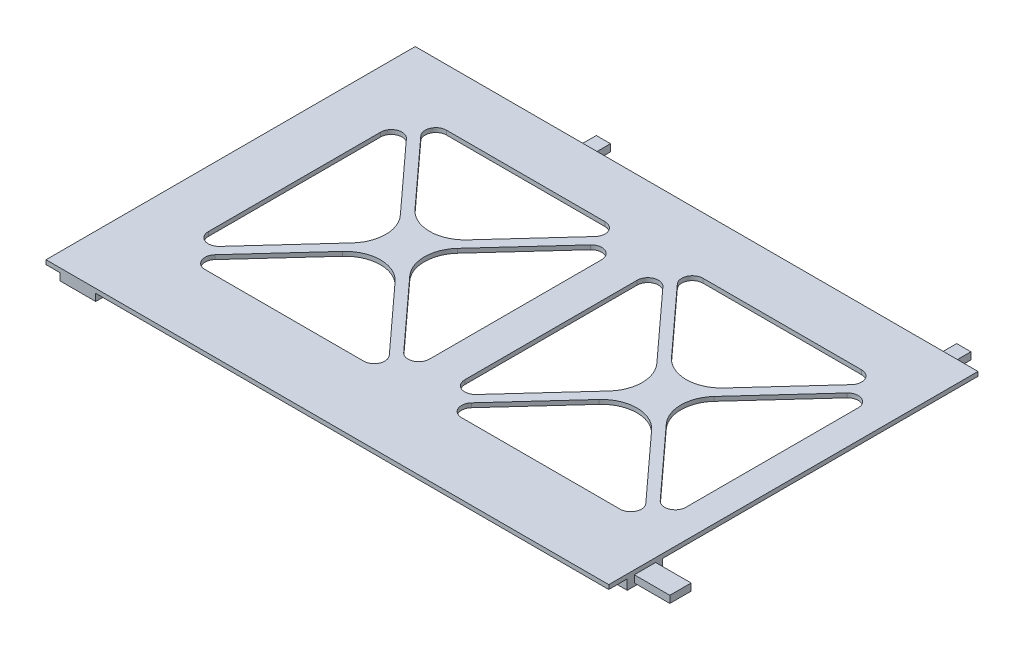
SolidWorks part; units mm, degrees
ref_plane "Front Plane" through (0, 0, 0) normal (0, 0, 1) x (1, 0, 0)
ref_plane "Top Plane" through (0, 0, 0) normal (0, 1, 0) x (1, 0, 0)
ref_plane "Right Plane" through (0, 0, 0) normal (1, 0, 0) x (0, 0, -1)
sketch "Sketch1" plane through (0, 0, 0) normal (0, 1, 0) x (1, 0, 0)
  line L0 (88.25, 88) -> (150.5, 88)
  line L1 (0, 0) -> (158.5, 0)
  line L2 (0, 0) -> (0, 104)
  line L3 (0, 104) -> (158.5, 104)
  line L4 (158.5, 0) -> (158.5, 104)
  line L5 (16, 88) -> (78.25, 88)
  line L6 (16, 88) -> (16, 20)
  line L7 (16, 20) -> (78.25, 20)
  line L8 (150.5, 88) -> (150.5, 20)
  line L10 (78.25, 88) -> (78.25, 20)
  line L12 (88.25, 88) -> (88.25, 20)
  line L13 (88.25, 20) -> (150.5, 20)
  dimension "D1" = 104
  dimension "D2" = 158.5
  dimension "D3" = 16
  dimension "D4" = 16
  dimension "D5" = 8
  dimension "D6" = 20
  dimension "D7" = 10
  dimension "D8" = 62.25
extrude "Boss-Extrude1" add sketch "Sketch1" along normal blind 1.2
sketch "Sketch2" plane through (0, 0, 0) normal (0, -1, 0) x (1, 0, 0)
  line L0 (158.5, 0) -> (158.5, -104) construction
  line L1 (151.5, -99) -> (147.5, -99)
  line L2 (151.5, -99) -> (151.5, -109)
  line L3 (151.5, -109) -> (147.5, -109)
  line L4 (147.5, -99) -> (147.5, -109)
  line L5 (158.5, -104) -> (0, -104) construction
  line L6 (0, -104) -> (0, 0) construction
  line L7 (46, -99) -> (50, -99)
  line L8 (46, -99) -> (46, -109)
  line L9 (46, -109) -> (50, -109)
  line L10 (50, -99) -> (50, -109)
  dimension "D1" = 7
  dimension "D2" = 4
  dimension "D3" = 5
  dimension "D4" = 5
  dimension "D5" = 46
  dimension "D6" = 4
  dimension "D7" = 5
  dimension "D8" = 5
extrude "Boss-Extrude2" add sketch "Sketch2" along normal blind 2
fillet "Fillet1" radius 2 4 edges at (50, 0, -101.5) (46, 0, -101.5) (147.5, 0, -101.5) (151.5, 0, -101.5)
sketch "Sketch3" plane through (0, 0, -104) normal (0, 0, -1) x (-1, 0, 0)
  line L0 (-158.5, 1.2) -> (0, 1.2) construction
  line L1 (-100.75, 1.2) -> (-90.75, 1.2)
  line L2 (-100.75, 1.2) -> (-100.75, -7.8)
  line L3 (-100.75, -7.8) -> (-90.75, -7.8)
  line L4 (-90.75, 1.2) -> (-90.75, -7.8)
  line L5 (-158.5, 1.2) -> (-158.5, 0) construction
  dimension "D1" = 9
  dimension "D2" = 57.75
  dimension "D3" = 10
extrude "Boss-Extrude3" add sketch "Sketch3" against normal blind 5
sketch "Sketch4" plane through (0, 0, -104) normal (0, 0, -1) x (-1, 0, 0)
  line L0 (-90.75, -7.8) -> (-90.75, 0) construction
  line L1 (-100.75, -7.8) -> (-90.75, -7.8) construction
  circle A0 centre (-95.75, -3.3) radius 1.3
  dimension "D1" = 2.6
  dimension "D2" = 5
  dimension "D3" = 4.5
extrude "Cut-Extrude1" cut sketch "Sketch4" against normal blind 5
sketch "Sketch5" plane through (0, 0, -99) normal (0, 0, 1) x (1, 0, 0)
  line L0 (100.75, -7.8) -> (90.75, -7.8) construction
  line L2 (92.25, -3.3) -> (92.25, -7.8)
  line L3 (92.25, -7.8) -> (99.25, -7.8)
  line L4 (99.25, -3.3) -> (99.25, -7.8)
  arc A0 (99.25, -3.3) -> (92.25, -3.3) centre (95.75, -3.3) ccw
  dimension "D1" = 7
extrude "Cut-Extrude2" cut sketch "Sketch5" against normal blind 3.8
fillet "Fillet2" radius 5 2 edges at (90.75, 0, -101.5) (100.75, 0, -101.5)
fillet "Fillet3" radius 2 2 edges at (90.75, -7.8, -101.5) (100.75, -7.8, -101.5)
sketch "Sketch6" plane through (0, 0, 0) normal (0, -1, 0) x (1, 0, 0)
  line L0 (158.5, 0) -> (158.5, -104) construction
  line L1 (158.5, -5.2) -> (60.5, -5.2)
  line L2 (158.5, -5.2) -> (158.5, -15.2)
  line L3 (158.5, -15.2) -> (60.5, -15.2)
  line L4 (60.5, -5.2) -> (60.5, -15.2)
  line L5 (0, 0) -> (158.5, 0) construction
  dimension "D1" = 5.2
  dimension "D2" = 10
  dimension "D3" = 98
extrude "Boss-Extrude4" add sketch "Sketch6" along normal blind 0.8
sketch "Sketch8" plane through (0, 0, 0) normal (0, -1, 0) x (1, 0, 0)
  line L0 (158.5, -5.2) -> (60.5, -5.2) construction
  line L1 (152.5, -7.2) -> (168.5, -7.2)
  line L2 (152.5, -7.2) -> (152.5, -13.2)
  line L3 (152.5, -13.2) -> (168.5, -13.2)
  line L4 (168.5, -7.2) -> (168.5, -13.2)
  line L5 (60.5, -15.2) -> (158.5, -15.2) construction
  line L6 (158.5, -15.2) -> (158.5, -5.2) construction
  dimension "D1" = 2
  dimension "D2" = 2
  dimension "D3" = 10
  dimension "D4" = 6
extrude "Boss-Extrude5" add sketch "Sketch8" along normal blind 2
sketch "Sketch9" plane through (0, 0, 0) normal (0, -1, 0) x (1, 0, 0)
  line L0 (60.5, -15.2) -> (158.5, -15.2) construction
  line L1 (158.5, -5.2) -> (152.5, -5.2)
  line L2 (158.5, -5.2) -> (158.5, -15.2)
  line L3 (158.5, -15.2) -> (152.5, -15.2)
  line L4 (152.5, -5.2) -> (152.5, -15.2)
  line L6 (60.5, -5.2) -> (57.5, -5.2)
  line L7 (60.5, -5.2) -> (60.5, -15)
  line L8 (60.5, -15) -> (57.5, -15)
  line L9 (57.5, -5.2) -> (57.5, -15)
  dimension "D1" = 6
  dimension "D2" = 3
extrude "Boss-Extrude6" add sketch "Sketch9" along normal blind 2.8
fillet "Fillet4" radius 3 1 edges at (57.5, 0, -10.1)
sketch "Sketch11" plane through (0, 0, 0) normal (0, -1, 0) x (1, 0, 0)
  line L0 (0, -104) -> (0, 0) construction
  line L1 (4, 0) -> (14, 0)
  line L2 (4, 0) -> (4, -71)
  line L3 (4, -71) -> (14, -71)
  line L4 (14, 0) -> (14, -71)
  line L5 (0, 0) -> (158.5, 0) construction
  dimension "D1" = 4
  dimension "D2" = 10
  dimension "D3" = 71
  dimension "D4" = 0
extrude "Boss-Extrude7" add sketch "Sketch11" along normal blind 2
sketch "Sketch12" plane through (0, 1.2, 0) normal (0, 1, 0) x (1, 0, 0)
  line L0 (22.585, 82.9774) -> (39.7395, 64.1857)
  line L1 (78.25, 88) -> (16, 88) construction
  line L2 (78.25, 20) -> (78.25, 88) construction
  line L3 (78.25, 29.736) -> (78.25, 51.0329)
  line L4 (78.25, 51.0329) -> (81.1217, 51.0329)
  line L5 (81.1217, 51.0329) -> (81.1217, 16.8323)
  line L6 (81.1217, 16.8323) -> (49.123, 16.8323)
  line L7 (49.123, 16.8323) -> (49.123, 20)
  line L8 (16, 20) -> (78.25, 20) construction
  line L9 (49.123, 20) -> (69.4493, 20)
  line L10 (71.665, 25.0226) -> (54.5105, 43.8143)
  line L11 (16, 88) -> (16, 20) construction
  line L12 (16, 78.264) -> (16, 63.3988)
  line L13 (16, 63.3988) -> (11.4085, 63.3988)
  line L14 (11.4085, 63.3988) -> (11.4085, 91.2087)
  line L15 (11.4085, 91.2087) -> (44.1798, 91.2087)
  line L16 (44.1798, 91.2087) -> (44.1798, 88)
  line L17 (44.1798, 88) -> (24.8007, 88)
  line L18 (71.665, 82.9774) -> (54.5105, 64.1857)
  line L19 (16, 29.736) -> (16, 46.9388)
  line L20 (16, 46.9388) -> (11.4085, 46.9388)
  line L21 (11.4085, 46.9388) -> (11.4085, 16.8323)
  line L22 (11.4085, 16.8323) -> (42.9175, 16.8323)
  line L23 (42.9175, 16.8323) -> (42.9175, 20)
  line L24 (42.9175, 20) -> (24.8007, 20)
  line L25 (22.585, 25.0226) -> (39.7395, 43.8143)
  line L26 (78.25, 78.264) -> (78.25, 63.3988)
  line L27 (78.25, 63.3988) -> (81.1217, 63.3988)
  line L28 (81.1217, 63.3988) -> (81.1217, 91.2087)
  line L29 (81.1217, 91.2087) -> (53.4527, 91.2087)
  line L30 (53.4527, 91.2087) -> (53.4527, 88)
  line L31 (53.4527, 88) -> (69.4493, 88)
  line L32 (39.0575, 47.258) -> (21.2156, 27.7134)
  line L33 (55.1925, 60.742) -> (73.0344, 80.2866)
  line L34 (55.1925, 47.258) -> (73.0344, 27.7134)
  line L35 (39.0575, 60.742) -> (21.2156, 80.2866)
  arc A0 (73.0344, 27.7134) -> (78.25, 29.736) centre (75.25, 29.736) ccw
  arc A1 (69.4493, 20) -> (71.665, 25.0226) centre (69.4493, 23) ccw
  arc A2 (24.8007, 20) -> (22.585, 25.0226) centre (24.8007, 23) cw
  arc A3 (21.2156, 27.7134) -> (16, 29.736) centre (19, 29.736) cw
  arc A4 (21.2156, 80.2866) -> (16, 78.264) centre (19, 78.264) ccw
  arc A5 (22.585, 82.9774) -> (24.8007, 88) centre (24.8007, 85) cw
  arc A6 (71.665, 82.9774) -> (69.4493, 88) centre (69.4493, 85) ccw
  arc A7 (73.0344, 80.2866) -> (78.25, 78.264) centre (75.25, 78.264) cw
  arc A8 (39.0575, 47.258) -> (39.0575, 60.742) centre (31.672, 54) ccw
  arc A9 (55.1925, 60.742) -> (55.1925, 47.258) centre (62.578, 54) ccw
  arc A10 (54.5105, 64.1857) -> (39.7395, 64.1857) centre (47.125, 70.9278) cw
  arc A11 (39.7395, 43.8143) -> (54.5105, 43.8143) centre (47.125, 37.0722) cw
  point P40 (0, 0)
  point P47 (78.25, 22)
  point P50 (76.25, 20)
  point P53 (18, 20)
  point P56 (16, 22)
  point P59 (16, 86)
  point P62 (18, 88)
  point P65 (76.25, 88)
  point P68 (78.25, 86)
  point P71 (45.2121, 54)
  point P74 (49.0379, 54)
  dimension "D15" = 3
  dimension "D16" = 10
  dimension "D1" = 3.2087
  dimension "D2" = 2.8717
  dimension "D3" = 2.8717
  dimension "D4" = 3.1677
  dimension "D5" = 4.5915
  dimension "D6" = 4.5915
  dimension "D7" = 2
  dimension "D8" = 2
  dimension "D9" = 2
  dimension "D10" = 2
  dimension "D11" = 2
  dimension "D12" = 2
  dimension "D13" = 2
  dimension "D14" = 2
extrude "Boss-Extrude8" add sketch "Sketch12" against normal up to surface (1.2 mm away) up to face at (47.125, 0, -54)
ref_plane "Plane1" through (83.25, 0, 0) normal (1, 0, 0) x (0, 0, -1)
mirror "Mirror1" about plane through (83.25, 0, 0) normal (1, 0, 0) of "Boss-Extrude8"
